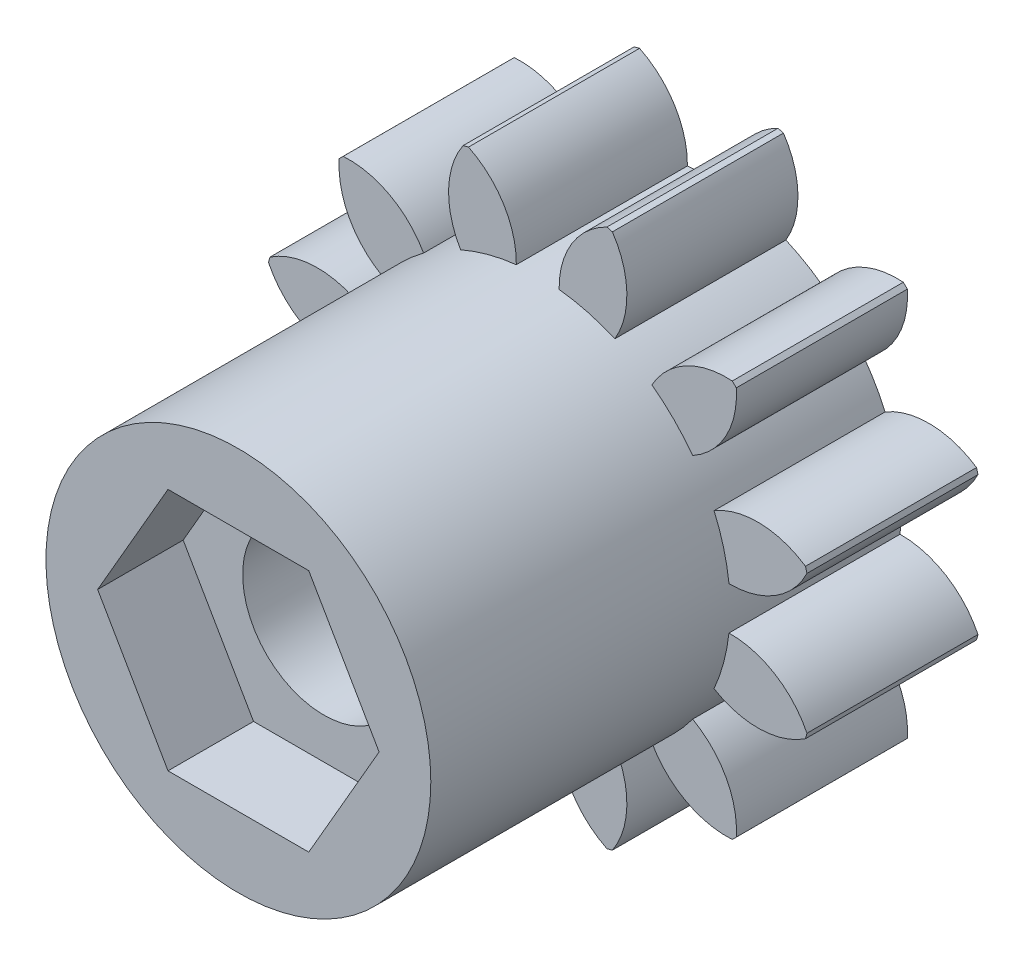
SolidWorks part; units mm, degrees
ref_plane "Front" through (0, 0, 0) normal (0, 0, 1) x (1, 0, 0)
ref_plane "Top" through (0, 0, 0) normal (0, 1, 0) x (1, 0, 0)
ref_plane "Right" through (0, 0, 0) normal (1, 0, 0) x (0, 0, -1)
sketch "Sketch1" plane through (0, 0, 0) normal (0, 0, 1) x (1, 0, 0)
  circle A0 centre (0, 0) radius 1
  circle A1 centre (0, 0) radius 6.5
extrude "Boss-Extrude1" add sketch "Sketch1" along normal blind 4
sketch "Sketch4" plane through (0, 0, 0) normal (0, 0, 1) x (1, 0, 0)
  line L0 (0, 4.5) -> (2.5, 4.5) construction
  line L1 (0, 4.5) -> (-2.5, 4.5) construction
  circle A0 centre (0, 0) radius 4.5
  circle A1 centre (0, 0) radius 7
  circle A2 centre (2.5, 4.5) radius 2
  circle A3 centre (-2.5, 4.5) radius 2
extrude "Cut-Extrude2" cut sketch "Sketch4" along normal through all contours A3 A0 A2 A1 region at (0, 6.0548, 0)
pattern_circular "CirPattern2" count 12 over 360 about axis through (0, 0, 4) along (0, 0, -1) of "Cut-Extrude2"
sketch "Sketch10" plane through (0, 0, 0) normal (0, 0, 1) x (1, 0, 0)
  line L0 (0, 4) -> (-5.1235, 4) construction
  line L1 (0, 4) -> (5.1235, 4) construction
  circle A0 centre (0, 0) radius 6.5
  circle A1 centre (0, 0) radius 4
  circle A2 centre (-2.5617, 4) radius 2.25
  circle A3 centre (2.5617, 4) radius 2.25
sketch "Sketch11" plane through (0, 0, 0) normal (0, 0, 1) x (1, 0, 0)
  circle A0 centre (0, 0) radius 4.5
extrude "Boss-Extrude2" add sketch "Sketch11" along normal blind 11
sketch "Sketch12" plane through (0, 0, 0) normal (0, 0, 1) x (1, 0, 0)
  line L1 (3.2909, 0) -> (1.6454, 2.85)
  line L2 (1.6454, 2.85) -> (-1.6454, 2.85)
  line L3 (-1.6454, 2.85) -> (-3.2909, 0)
  line L4 (-3.2909, 0) -> (-1.6454, -2.85)
  line L5 (-1.6454, -2.85) -> (1.6454, -2.85)
  line L6 (1.6454, -2.85) -> (3.2909, 0)
  circle A0 centre (0, 0) radius 2.85 construction
  dimension "D1" = 5.7
extrude "Cut-Extrude3" cut sketch "Sketch12" against normal blind 2 from offset 11
sketch "Sketch13" plane through (0, 0, 0) normal (0, 0, 1) x (1, 0, 0)
  circle A0 centre (0, 0) radius 1.9
extrude "Cut-Extrude4" cut sketch "Sketch13" along normal through all contours A0 region at (0, 0, 0)
